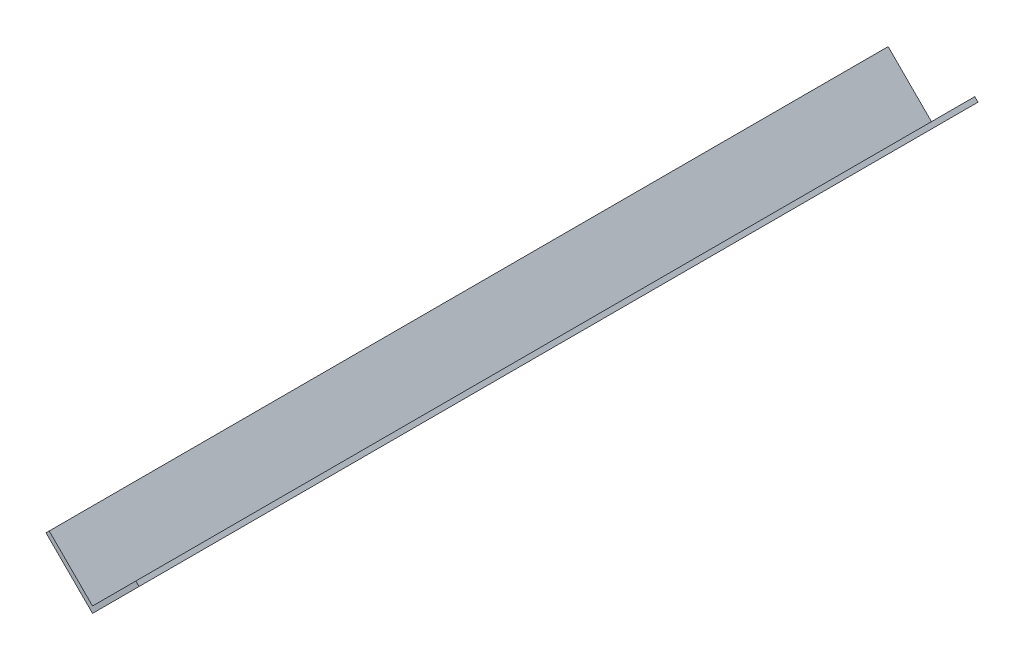
SolidWorks part; units mm, degrees
material "6061 Alloy"
ref_plane "Front Plane" through (0, 0, 0) normal (0, 0, 1) x (1, 0, 0)
ref_plane "Top Plane" through (0, 0, 0) normal (0, 1, 0) x (1, 0, 0)
ref_plane "Right Plane" through (0, 0, 0) normal (1, 0, 0) x (0, 0, -1)
sketch "Sketch1" plane through (0, 0, 0) normal (0, 0, 1) x (1, 0, 0)
  line L0 (0, 0) -> (-17.9605, 17.9605)
  line L1 (-17.9605, 17.9605) -> (-16.7257, 19.1953)
  line L2 (-16.7257, 19.1953) -> (0, 2.4696)
  line L3 (0, 2.4696) -> (16.7257, 19.1953)
  line L4 (16.7257, 19.1953) -> (17.9605, 17.9605)
  line L5 (17.9605, 17.9605) -> (0, 0)
  dimension "D1" = 1.7463
  dimension "D2" = 25.4
extrude "Boss-Extrude1" add sketch "Sketch1" along normal blind 323.85
sketch "Sketch3" [suppressed] plane through (0, 0, 0) normal (1, 0, 0) x (0, 0, -1)
  line L0 (-285.75, 16.0203) -> (-323.85, 16.0203) construction
  line L6 (-200.025, 19.1953) -> (-206.375, 19.1953)
  line L7 (-206.375, 19.1953) -> (-206.375, 16.0203)
  line L8 (-200.025, 16.0203) -> (-200.025, 19.1953)
  line L9 (-117.475, 19.1953) -> (-123.825, 19.1953)
  line L10 (-123.825, 19.1953) -> (-123.825, 16.0203)
  line L11 (-117.475, 16.0203) -> (-117.475, 19.1953)
  line L16 (-34.925, 19.1953) -> (-41.275, 19.1953)
  line L17 (-41.275, 19.1953) -> (-41.275, 16.0203)
  line L22 (-34.925, 16.0203) -> (-34.925, 19.1953)
  line L28 (-323.85, 0) -> (-323.85, 17.9605) construction
  line L29 (-285.75, 16.0203) -> (-203.2, 16.0203) construction
  line L30 (-288.925, 19.1953) -> (-288.925, 16.0203)
  line L31 (-323.85, 19.1953) -> (0, 19.1953) construction
  line L32 (-282.575, 16.0203) -> (-282.575, 19.1953)
  line L33 (-282.575, 19.1953) -> (-288.925, 19.1953)
  line L34 (-203.2, 16.0203) -> (-120.65, 16.0203) construction
  line L35 (-120.65, 16.0203) -> (-38.1, 16.0203) construction
  line L36 (-38.1, 16.0203) -> (0, 16.0203) construction
  line L37 (0, 0) -> (0, 17.9605) construction
  arc A0 (-288.925, 16.0203) -> (-282.575, 16.0203) centre (-285.75, 16.0203) ccw
  arc A1 (-206.375, 16.0203) -> (-200.025, 16.0203) centre (-203.2, 16.0203) ccw
  arc A2 (-123.825, 16.0203) -> (-117.475, 16.0203) centre (-120.65, 16.0203) ccw
  arc A3 (-41.275, 16.0203) -> (-34.925, 16.0203) centre (-38.1, 16.0203) ccw
  dimension "D1" = 82.55
  dimension "D5" = 3.175
  dimension "D4" = 6.35
extrude "Cut-Extrude2" [suppressed] cut sketch "Sketch3" against normal through all both and the other way through all
sketch "Sketch4" [suppressed] plane through (0, 0, 0) normal (0.7071, -0.7071, 0) x (0, 0, -1)
  line L0 (-288.925, 25.4) -> (-288.925, 19.5947)
  line L1 (-282.575, 19.5947) -> (-282.575, 25.4)
  line L17 (-282.575, 25.4) -> (-288.925, 25.4)
  line L21 (-206.375, 25.4) -> (-206.375, 19.5947)
  line L22 (-200.025, 19.5947) -> (-200.025, 25.4)
  line L23 (-200.025, 25.4) -> (-206.375, 25.4)
  line L24 (-123.825, 25.4) -> (-123.825, 19.5947)
  line L25 (-117.475, 19.5947) -> (-117.475, 25.4)
  line L26 (-117.475, 25.4) -> (-123.825, 25.4)
  line L27 (-41.275, 25.4) -> (-41.275, 19.5947)
  line L28 (-34.925, 19.5947) -> (-34.925, 25.4)
  line L29 (-34.925, 25.4) -> (-41.275, 25.4)
  line L30 (-41.275, 22.6561) -> (-41.275, 25.4) construction
  arc A0 (-288.925, 19.5947) -> (-282.575, 19.5947) centre (-285.75, 19.5947) ccw
  arc A2 (-206.375, 19.5947) -> (-200.025, 19.5947) centre (-203.2, 19.5947) ccw
  arc A5 (-123.825, 19.5947) -> (-117.475, 19.5947) centre (-120.65, 19.5947) ccw
  arc A6 (-41.275, 19.5947) -> (-34.925, 19.5947) centre (-38.1, 19.5947) ccw
  ellipse E3 centre (-285.75, 20.9099) end of major axis (-285.75, 25.4) minor radius 3.175 (-288.925, 20.9099) -> (-282.575, 20.9099) ccw construction
  dimension "D1" = 4
extrude "Cut-Extrude3" [suppressed] cut sketch "Sketch4" against normal through all both and the other way through all
mirror "Mirror1" [suppressed] about plane through (0, 0, 0) normal (1, 0, 0)
